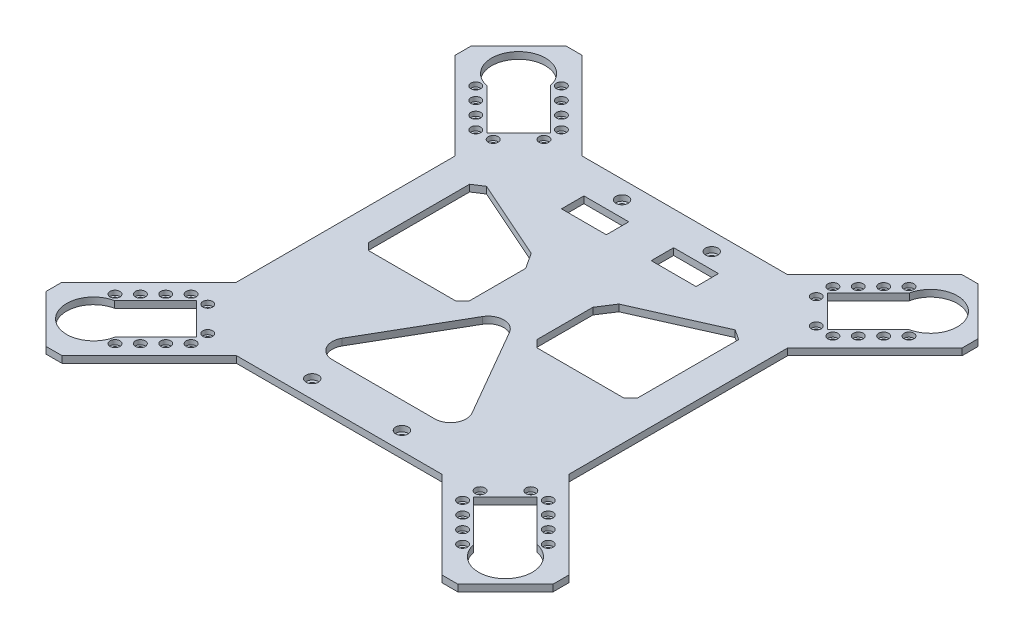
SolidWorks part; units mm, degrees
material "Thornel Mat VMA"
ref_plane "Front Plane" through (0, 0, 0) normal (0, 0, 1) x (1, 0, 0)
ref_plane "Top Plane" through (0, 0, 0) normal (0, 1, 0) x (1, 0, 0)
ref_plane "Right Plane" through (0, 0, 0) normal (1, 0, 0) x (0, 0, -1)
sketch "Sketch1" plane through (0, 0, 0) normal (0, 1, 0) x (1, 0, 0)
  line L0 (-60, 100) -> (-122.1499, 162.1499) construction
  line L1 (-74.1421, -30) -> (-74.1421, -85.8579)
  line L2 (74.1421, -30) -> (74.1421, -85.8579)
  line L5 (-60, 100) -> (60, -100) construction
  line L6 (-60, -100) -> (60, 100) construction
  line L11 (-45.8579, 114.1421) -> (-84.7487, 153.033)
  line L13 (-74.1421, 85.8579) -> (-113.033, 124.7487)
  line L14 (-91.8198, 153.033) -> (-113.033, 131.8198)
  line L15 (-84.7487, 153.033) -> (-91.8198, 153.033)
  line L16 (-113.033, 124.7487) -> (-113.033, 131.8198)
  line L17 (0, 118.7449) -> (0, 114.1421) construction
  line L18 (113.033, 124.7487) -> (113.033, 131.8198)
  line L19 (91.8198, 153.033) -> (113.033, 131.8198)
  line L20 (84.7487, 153.033) -> (91.8198, 153.033)
  line L21 (74.1421, 85.8579) -> (113.033, 124.7487)
  line L24 (45.8579, 114.1421) -> (84.7487, 153.033)
  line L25 (-95.3553, 0) -> (90.6066, 0) construction
  line L26 (-113.033, -124.7487) -> (-113.033, -131.8198)
  line L27 (-91.8198, -153.033) -> (-113.033, -131.8198)
  line L28 (-84.7487, -153.033) -> (-91.8198, -153.033)
  line L29 (-45.8579, -114.1421) -> (-84.7487, -153.033)
  line L30 (-74.1421, -85.8579) -> (-113.033, -124.7487)
  line L35 (74.1421, -85.8579) -> (113.033, -124.7487)
  line L36 (113.033, -124.7487) -> (113.033, -131.8198)
  line L37 (91.8198, -153.033) -> (113.033, -131.8198)
  line L38 (84.7487, -153.033) -> (91.8198, -153.033)
  line L39 (45.8579, -114.1421) -> (84.7487, -153.033)
  line L40 (45.8579, 114.1421) -> (-45.8579, 114.1421)
  line L41 (-45.8579, -114.1421) -> (45.8579, -114.1421)
  line L42 (74.1421, 85.8579) -> (74.1421, 30)
  line L43 (-74.1421, 85.8579) -> (-74.1421, 30)
  line L44 (74.1421, 30) -> (90.6066, 20)
  line L46 (90.6066, -20) -> (74.1421, -30)
  line L47 (90.6066, 20) -> (145.6066, 20)
  line L48 (150.6066, 15) -> (150.6066, -15)
  line L49 (145.6066, -20) -> (90.6066, -20)
  line L50 (145.6066, 20) -> (150.6066, 15)
  line L51 (150.6066, -15) -> (145.6066, -20)
  line L52 (-150.6066, -15) -> (-145.6066, -20)
  line L53 (-150.6066, 15) -> (-150.6066, -15)
  line L54 (-145.6066, 20) -> (-150.6066, 15)
  line L55 (-145.6066, -20) -> (-90.6066, -20)
  line L56 (-90.6066, 20) -> (-145.6066, 20)
  line L58 (-90.6066, -20) -> (-74.1421, -30)
  line L59 (-74.1421, 30) -> (-90.6066, 20)
  line L60 (0, 100) -> (0, -122.5689) construction
  point P0 (0, 0)
  point P12 (-88.2843, 156.5685)
  point P14 (-116.5685, 128.2843)
  point P42 (150.6066, 20)
  point P46 (150.6066, -20)
  dimension "D1" = 200
  dimension "D2" = 120
  dimension "D3" = 20
  dimension "D4" = 60
  dimension "D5" = 20
  dimension "D6" = 60
  dimension "D7" = 30
  dimension "D8" = 30
  dimension "D9" = 40
  dimension "D10" = 20
  dimension "D13" = 30
  dimension "D14" = 60
  dimension "D15" = 15
extrude "Boss-Extrude1" add sketch "Sketch1" along normal blind 3
sketch "Sketch2" plane through (0, 3, 0) normal (0, 1, 0) x (1, 0, 0)
  line L0 (150.6066, -15) -> (150.6066, 15) construction
  line L1 (103.1066, 10) -> (128.9734, 10)
  line L2 (103.1066, 10) -> (103.1066, -10)
  line L3 (103.1066, -10) -> (128.9734, -10)
  line L4 (0, 114.1421) -> (0, -114.1421) construction
  line L5 (145.6066, 20) -> (90.6066, 20) construction
  line L6 (45.8579, 114.1421) -> (-45.8579, 114.1421) construction
  line L7 (-45.8579, -114.1421) -> (45.8579, -114.1421) construction
  line L8 (-103.1066, -10) -> (-128.9734, -10)
  line L9 (-103.1066, 10) -> (-103.1066, -10)
  line L10 (-103.1066, 10) -> (-128.9734, 10)
  arc A0 (128.9734, -10) -> (128.9734, 10) centre (135.6066, 0) ccw
  arc A1 (-128.9734, -10) -> (-128.9734, 10) centre (-135.6066, 0) cw
  dimension "D1" = 24
  dimension "D2" = 15
  dimension "D3" = 20
  dimension "D4" = 10
  dimension "D5" = 32.5
  dimension "D6" = 20
extrude "Cut-Extrude1" cut sketch "Sketch2" against normal blind 10
sketch "Sketch4" plane through (0, 3, 0) normal (0, 1, 0) x (1, 0, 0)
  line L0 (-102.4264, 142.4264) -> (-100.3051, 140.3051) construction
  line L1 (-91.8198, 153.033) -> (-113.033, 131.8198) construction
  line L2 (-75.9099, 101.7678) -> (-61.7678, 115.9099)
  line L3 (-61.7678, 115.9099) -> (-80.0583, 134.2005)
  line L4 (0, 114.1421) -> (0, -114.1421) construction
  line L5 (-94.2005, 120.0583) -> (-75.9099, 101.7678)
  line L6 (-68.8388, 108.8388) -> (-51.636, 91.636) construction
  line L7 (45.8579, 114.1421) -> (-45.8579, 114.1421) construction
  line L8 (-45.8579, -114.1421) -> (45.8579, -114.1421) construction
  line L9 (68.8388, 108.8388) -> (51.636, 91.636) construction
  line L10 (102.4264, 142.4264) -> (100.3051, 140.3051) construction
  line L11 (94.2005, 120.0583) -> (75.9099, 101.7678)
  line L12 (61.7678, 115.9099) -> (80.0583, 134.2005)
  line L13 (75.9099, 101.7678) -> (61.7678, 115.9099)
  line L14 (-103.1066, 0) -> (103.1066, 0) construction
  line L15 (-103.1066, -10) -> (-103.1066, 10) construction
  line L16 (103.1066, 10) -> (103.1066, -10) construction
  line L17 (102.4264, -142.4264) -> (100.3051, -140.3051) construction
  line L18 (68.8388, -108.8388) -> (51.636, -91.636) construction
  line L19 (-68.8388, -108.8388) -> (-51.636, -91.636) construction
  line L20 (-102.4264, -142.4264) -> (-100.3051, -140.3051) construction
  line L21 (75.9099, -101.7678) -> (61.7678, -115.9099)
  line L22 (61.7678, -115.9099) -> (80.0583, -134.2005)
  line L23 (94.2005, -120.0583) -> (75.9099, -101.7678)
  line L24 (-94.2005, -120.0583) -> (-75.9099, -101.7678)
  line L25 (-61.7678, -115.9099) -> (-80.0583, -134.2005)
  line L26 (-75.9099, -101.7678) -> (-61.7678, -115.9099)
  arc A0 (-80.0583, 134.2005) -> (-94.2005, 120.0583) centre (-91.8198, 131.8198) ccw
  arc A1 (80.0583, 134.2005) -> (94.2005, 120.0583) centre (91.8198, 131.8198) cw
  arc A2 (80.0583, -134.2005) -> (94.2005, -120.0583) centre (91.8198, -131.8198) ccw
  arc A3 (-80.0583, -134.2005) -> (-94.2005, -120.0583) centre (-91.8198, -131.8198) cw
  dimension "D1" = 24
  dimension "D2" = 15
  dimension "D3" = 32.5
  dimension "D4" = 20
  dimension "D5" = 10
extrude "Cut-Extrude2" cut sketch "Sketch4" against normal blind 10
hole_wizard "CBORE for M2 SHCS1" positions "Sketch7" profile "Sketch6" counterbore size "M2" standard "Ansi Metric" end condition through all
sketch "Sketch7" plane through (0, 3, 0) normal (0, 1, 0) x (-1, 0, 0)
  line L0 (-128.9734, -10) -> (-103.1066, -10) construction
  line L1 (-103.1066, -10) -> (-103.1066, 10) construction
  line L2 (-103.1066, 10) -> (-128.9734, 10) construction
  line L3 (-80.0583, -134.2005) -> (-61.7678, -115.9099) construction
  line L4 (-61.7678, -115.9099) -> (-75.9099, -101.7678) construction
  line L5 (-75.9099, -101.7678) -> (-94.2005, -120.0583) construction
  point P0 (-104.8566, -13.5)
  point P1 (-112.8566, -13.5)
  point P3 (-120.8566, -13.5)
  point P5 (-128.8566, -13.5)
  point P7 (-60.5303, -119.6222)
  point P9 (-66.1872, -125.2791)
  point P11 (-71.844, -130.9359)
  point P13 (-77.5009, -136.5928)
  point P15 (-79.6222, -100.5303)
  point P17 (-85.2791, -106.1872)
  point P19 (-90.9359, -111.844)
  point P21 (-96.5928, -117.5009)
  point P31 (-104.8566, 13.5)
  point P33 (-112.8566, 13.5)
  point P35 (-120.8566, 13.5)
  point P37 (-128.8566, 13.5)
  point P59 (-60.7071, -112.0208)
  point P61 (-72.0208, -100.7071)
  point P63 (-99.6066, -8)
  point P65 (-99.6066, 8)
  dimension "D1" = 3.5
  dimension "D2" = 8
  dimension "D3" = 8
  dimension "D4" = 8
  dimension "D5" = 3.5
  dimension "D6" = 1.75
  dimension "D7" = 8
  dimension "D8" = 8
  dimension "D9" = 8
  dimension "D10" = 1.75
  dimension "D11" = 3.5
  dimension "D12" = 8
  dimension "D13" = 8
  dimension "D14" = 8
  dimension "D15" = 3.5
  dimension "D16" = 3.5
  dimension "D17" = 3.5
  dimension "D18" = 3.5
  dimension "D19" = 1.75
  dimension "D20" = 8
  dimension "D21" = 8
  dimension "D22" = 8
  dimension "D23" = 3.5
  dimension "D24" = 3.5
  dimension "D25" = 3.5
  dimension "D26" = 3.5
  dimension "D27" = 1.75
  dimension "D28" = 3.5
  dimension "D29" = 3.5
  dimension "D30" = 2
  dimension "D31" = 2
  dimension "D32" = 3.5
  dimension "D33" = 3.5
  dimension "D34" = 2
  dimension "D35" = 2
sketch "Sketch6" plane through (104.8566, 3, -13.5) normal (1, 0, 0) x (0, 0, 1)
  line L0 (0, 0) -> (0, 3)
  line L1 (0, 3) -> (1.2, 3)
  line L3 (1.2, 3) -> (1.2, 2)
  line L4 (1.2, 2) -> (2.2, 2)
  line L5 (2.2, 2) -> (2.2, 0)
  line L7 (2.2, 0) -> (0, 0)
  line L11 (0, -6.35) -> (0, 107.95) construction
  dimension "Thru Hole Dia." = 2.4
  dimension "Thru Hole Depth" = 3
  dimension "C'Bore Dia." = 4.4
  dimension "C'Bore Depth" = 2
mirror "Mirror1" about plane through (0, 0, 0) normal (1, 0, 0) of "CBORE for M2 SHCS1"
mirror "Mirror2" about plane through (0, 0, 0) normal (0, 0, 1) of "Mirror1", "CBORE for M2 SHCS1"
sketch "Sketch8" plane through (0, 3, 0) normal (0, 1, 0) x (1, 0, 0)
  line L0 (-45.8579, -114.1421) -> (45.8579, -114.1421) construction
  line L1 (30, -99.1421) -> (10, -99.1421)
  line L2 (30, -99.1421) -> (30, -89.1421)
  line L3 (30, -89.1421) -> (10, -89.1421)
  line L4 (10, -99.1421) -> (10, -89.1421)
  line L5 (-10, -99.1421) -> (-30, -99.1421)
  line L6 (-10, -99.1421) -> (-10, -89.1421)
  line L7 (-10, -89.1421) -> (-30, -89.1421)
  line L8 (-30, -99.1421) -> (-30, -89.1421)
  line L9 (-45.8579, -114.1421) -> (45.8579, -114.1421) construction
  line L10 (-20, -28.1625) -> (-55, -28.1625)
  line L11 (30, -20) -> (-30, -20)
  line L12 (30, -20) -> (30, -10)
  line L13 (30, -10) -> (-30, -10)
  line L14 (-30, -20) -> (-30, -10)
  line L15 (-60, -33.1625) -> (-60, -78.1625)
  line L16 (-55.4309, -81.1318) -> (-19.5691, -65.1932)
  line L17 (-15, -58.1625) -> (-15, -33.1625)
  line L18 (-60, -78.1625) -> (-55.4309, -81.1318)
  line L19 (-19.5691, -65.1932) -> (-15, -58.1625)
  line L20 (-15, -33.1625) -> (-20, -28.1625)
  line L21 (-55, -28.1625) -> (-60, -33.1625)
  line L22 (55, -28.1625) -> (20, -28.1625)
  line L23 (15, -33.1625) -> (15, -58.1625)
  line L24 (19.5691, -65.1932) -> (55.4309, -81.1318)
  line L25 (60, -78.1625) -> (60, -33.1625)
  line L26 (55.4309, -81.1318) -> (60, -78.1625)
  line L27 (15, -58.1625) -> (19.5691, -65.1932)
  line L28 (20, -28.1625) -> (15, -33.1625)
  line L29 (60, -33.1625) -> (55, -28.1625)
  line L30 (84.5185, 0) -> (-74.8348, 0) construction
  line L31 (-20, 28.1625) -> (-55, 28.1625)
  line L32 (-55, 28.1625) -> (-60, 33.1625)
  line L33 (-60, 33.1625) -> (-60, 78.1625)
  line L34 (-60, 78.1625) -> (-55.4309, 81.1318)
  line L35 (-55.4309, 81.1318) -> (-19.5691, 65.1932)
  line L36 (-19.5691, 65.1932) -> (-15, 58.1625)
  line L37 (-15, 58.1625) -> (-15, 33.1625)
  line L38 (-15, 33.1625) -> (-20, 28.1625)
  line L39 (20, 28.1625) -> (15, 33.1625)
  line L40 (15, 33.1625) -> (15, 58.1625)
  line L41 (15, 58.1625) -> (19.5691, 65.1932)
  line L42 (19.5691, 65.1932) -> (55.4309, 81.1318)
  line L43 (55.4309, 81.1318) -> (60, 78.1625)
  line L44 (60, 78.1625) -> (60, 33.1625)
  line L45 (60, 33.1625) -> (55, 28.1625)
  line L46 (55, 28.1625) -> (20, 28.1625)
  line L47 (30, 99.1421) -> (10, 99.1421)
  line L48 (30, 99.1421) -> (30, 89.1421)
  line L49 (30, 89.1421) -> (10, 89.1421)
  line L50 (10, 99.1421) -> (10, 89.1421)
  line L51 (-10, 99.1421) -> (-10, 89.1421)
  line L52 (-10, 99.1421) -> (-30, 99.1421)
  line L53 (-30, 99.1421) -> (-30, 89.1421)
  line L54 (-10, 89.1421) -> (-30, 89.1421)
  point P10 (0, -114.1421)
  point P13 (0, -114.1421)
  point P18 (-15, -28.1625)
  point P20 (-60, -28.1625)
  point P22 (-60, -83.1625)
  point P23 (-15, -63.1625)
  point P31 (60, -28.1625)
  point P32 (15, -28.1625)
  point P34 (15, -63.1625)
  point P35 (60, -83.1625)
  dimension "D1" = 20
  dimension "D2" = 20
  dimension "D3" = 15
  dimension "D4" = 15
  dimension "D5" = 10
  dimension "D6" = 10
  dimension "D7" = 10
  dimension "D8" = 10
  dimension "D9" = 10
  dimension "D10" = 60
  dimension "D11" = 10
  dimension "D12" = 45
  dimension "D13" = 55
  dimension "D14" = 35
  dimension "D15" = 55
  dimension "D16" = 35
  dimension "D17" = 45
  dimension "D18" = 15
  dimension "D23" = 15
extrude "Cut-Extrude3" cut sketch "Sketch8" against normal blind 10
hole_wizard "CBORE for M2.5 SHCS1" positions "Sketch11" profile "Sketch10" counterbore size "M2.5" standard "Ansi Metric" end condition through all
sketch "Sketch11" plane through (0, 3, 0) normal (0, 1, 0) x (-1, 0, 0)
  line L0 (30, 99.1421) -> (10, 99.1421) construction
  line L1 (-10, 99.1421) -> (-30, 99.1421) construction
  line L2 (10, -99.1421) -> (30, -99.1421) construction
  line L3 (-30, -99.1421) -> (-10, -99.1421) construction
  point P0 (20, -106.1421)
  point P1 (-20, -106.1421)
  point P3 (20, 106.1421)
  point P5 (-20, 106.1421)
  dimension "D1" = 7
  dimension "D2" = 7
  dimension "D3" = 10
  dimension "D4" = 10
  dimension "D5" = 7
  dimension "D6" = 7
  dimension "D7" = 10
  dimension "D8" = 10
sketch "Sketch10" plane through (-20, 3, -106.1421) normal (1, 0, 0) x (0, 0, 1)
  line L0 (0, 0) -> (0, 3)
  line L1 (0, 3) -> (1.45, 3)
  line L3 (1.45, 3) -> (1.45, 2.5)
  line L4 (1.45, 2.5) -> (2.75, 2.5)
  line L5 (2.75, 2.5) -> (2.75, 0)
  line L7 (2.75, 0) -> (0, 0)
  line L11 (0, -6.35) -> (0, 107.95) construction
  dimension "Thru Hole Dia." = 2.9
  dimension "Thru Hole Depth" = 3
  dimension "C'Bore Dia." = 5.5
  dimension "C'Bore Depth" = 2.5
sketch "Croquis1" plane through (0, 3, 0) normal (0, 1, 0) x (-1, 0, 0)
  line L0 (186.8809, -30) -> (-169.671, -30)
  line L2 (-169.671, -30) -> (-169.671, 164.8)
  line L3 (-169.671, 164.8) -> (186.8809, 164.8)
  line L4 (186.8809, 164.8) -> (186.8809, -30)
extrude "Cortar-Extruir1" cut sketch "Croquis1" along normal blind 848 and the other way blind 962
sketch "Croquis3" plane through (0, 3, 0) normal (0, 1, 0) x (1, 0, 0)
  line L0 (-74.1421, -40) -> (-74.1421, 30)
  line L2 (-74.1421, 30) -> (74.1421, 30)
  line L3 (74.1421, 30) -> (74.1421, -40)
  line L4 (-74.1421, -40) -> (74.1421, -40)
  line L6 (-74.1421, -40) -> (74.1421, -40)
  line L7 (-74.1421, -40) -> (-74.1421, 30)
  line L8 (-74.1421, 30) -> (74.1421, 30)
  line L9 (74.1421, -40) -> (74.1421, 30)
extrude "Saliente-Extruir3" add sketch "Croquis3" against normal blind 3 contours L0 L4 L3 L2 region at (0, 3, 5)
sketch "Croquis5" plane through (0, 3, 0) normal (0, 1, 0) x (-1, 0, 0)
  line L0 (45.8579, -114.1421) -> (45.8579, 40) construction
  line L1 (74.1421, 40) -> (-74.1421, 40) construction
  line L2 (-45.8579, -114.1421) -> (-45.8579, 40) construction
sketch "Croquis7" plane through (0, 3, 0) normal (0, 1, 0) x (-1, 0, 0)
  line L0 (-74.1421, -85.8579) -> (-45.8579, -85.8579) construction
  line L1 (-45.8579, -114.1421) -> (-45.8579, 40) construction
  line L2 (-45.8579, 40) -> (-45.8579, 11.7157) construction
  line L3 (-45.8579, 11.7157) -> (-74.1421, 11.7157) construction
  line L4 (-74.1421, 40) -> (-74.1421, -85.8579) construction
  line L5 (-74.1421, 11.7157) -> (-45.8579, 11.7157) construction
  line L6 (-45.8579, 11.7157) -> (74.1421, 11.7157) construction
  line L7 (74.1421, -85.8579) -> (74.1421, 40) construction
  line L8 (74.1421, 11.7157) -> (45.8579, 40) construction
  line L9 (-74.1421, 11.7157) -> (-45.8579, 40) construction
  line L10 (-45.8579, 11.7157) -> (-102.4264, 68.2843) construction
  line L11 (-45.8579, -85.8579) -> (-102.4264, -142.4264) construction
  line L12 (-113.033, -131.8198) -> (-91.8198, -153.033) construction
  line L13 (-102.4264, 68.2843) -> (-91.8198, 78.8909)
  line L14 (-45.8579, 40) -> (-84.7487, 78.8909)
  line L15 (-113.033, 50.6066) -> (-74.1421, 11.7157)
  line L16 (-84.7487, 78.8909) -> (-84.4653, 78.9354)
  line L17 (-113.033, -131.8198) -> (-132.5778, -112.275) construction
  line L18 (-74.1421, -85.8579) -> (-138.5229, -150.2386) construction
  line L19 (-45.8579, 40) -> (-74.1421, 11.7157)
  line L20 (-91.8198, 78.8909) -> (-84.7487, 78.8909)
  line L21 (-74.1421, 11.7157) -> (-113.033, 50.6066)
  line L22 (-113.033, 57.6777) -> (-102.4264, 68.2843)
  line L23 (-113.033, 57.6777) -> (-113.033, 50.6066)
  dimension "D1" = 28.2843
  dimension "D2" = 28.2843
extrude "Saliente-Extruir4" add sketch "Croquis7" against normal blind 3 contours L22 L23 L15 L19 L14 L20 L13 region at (81.0023, 3, 46.8602)
sketch "Croquis9" plane through (0, 3, 0) normal (0, 1, 0) x (-1, 0, 0)
  line L0 (-102.4264, 68.2843) -> (-38.465, 4.3229) construction
  line L1 (-113.033, 57.6777) -> (-91.8198, 78.8909) construction
  line L2 (-74.1421, 11.7157) -> (-45.8579, 40) construction
  line L3 (-45.8579, -114.1421) -> (-74.1421, -85.8579) construction
  line L4 (-60, 25.8579) -> (-68.8388, 34.6967) construction
  line L5 (-60, 25.8579) -> (-91.8198, 57.6777) construction
  line L6 (-60, -100) -> (-68.8388, -108.8388) construction
  line L7 (-61.7678, -115.9099) -> (-75.9099, -101.7678) construction
  line L8 (-68.8388, 34.6967) -> (-75.9099, 27.6256) construction
  line L9 (-68.8388, 34.6967) -> (-61.7678, 41.7678) construction
  line L10 (-61.7678, 41.7678) -> (-75.9099, 27.6256)
  line L11 (-61.7678, 41.7678) -> (-86.1616, 66.1616) construction
  line L12 (-75.9099, 27.6256) -> (-95.9758, 47.6915) construction
  line L13 (-61.7678, 41.7678) -> (-80.0583, 60.0583)
  line L14 (-75.9099, 27.6256) -> (-94.2005, 45.9162)
  line L15 (-68.8388, -108.8388) -> (-91.8198, -131.8198) construction
  arc A0 (-94.2005, 45.9162) -> (-80.0583, 60.0583) centre (-91.8198, 57.6777) cw
  dimension "D1" = 12
  dimension "D2" = 10
  dimension "D3" = 10
extrude "Cortar-Extruir3" cut sketch "Croquis9" against normal blind 3
sketch "Croquis10" plane through (0, 3, 0) normal (0, 1, 0) x (-1, 0, 0)
  line L0 (-105.6578, 43.2313) -> (-101.0616, 47.8275) construction
  line L1 (-60.5303, -119.6222) -> (-50.4541, -109.5459) construction
  line L2 (-59.0233, -127.3076) -> (-63.7541, -122.846) construction
  line L3 (-84.7487, -153.033) -> (-45.8579, -114.1421) construction
  line L4 (-45.8579, -114.1421) -> (-74.1421, -85.8579) construction
  line L5 (-66.1872, -125.2791) -> (-14.5561, -155.2155) construction
  line L6 (-113.033, 50.6066) -> (-74.1421, 11.7157) construction
  line L7 (-101.0616, 47.8275) -> (-69.5459, 16.3119) construction
  line L8 (-69.5459, 16.3119) -> (-79.6222, 26.3882) construction
  line L9 (-79.6222, 26.3882) -> (-85.2791, 32.045) construction
  line L10 (-74.1421, 11.7157) -> (-69.5459, 16.3119) construction
  line L11 (-69.5459, 16.3119) -> (-45.8579, 40) construction
  line L12 (-85.2791, 32.045) -> (-90.9359, 37.7019) construction
  line L13 (-90.9359, 37.7019) -> (-96.5928, 43.3588) construction
  circle A0 centre (-79.6222, 26.3882) radius 1.2
  circle A1 centre (-85.2791, 32.045) radius 1.2
  circle A2 centre (-90.9359, 37.7019) radius 1.2
  circle A3 centre (-96.5928, 43.3588) radius 1.2
  dimension "D3" = 14.25
  dimension "D5" = 8
  dimension "D7" = 2.4
  dimension "D9" = 2.4
  dimension "D10" = 2.4
  dimension "D8" = 2.4
  dimension "D1" = 6.5
  dimension "D2" = 6.5
  dimension "D4" = 8
  dimension "D6" = 8
extrude "Cortar-Extruir13" cut sketch "Croquis10" against normal blind 3
sketch "Croquis22" plane through (0, 3, 0) normal (0, 1, 0) x (-1, 0, 0)
  circle A0 centre (-79.6222, 26.3882) radius 2.2
  circle A1 centre (-85.2791, 32.045) radius 2.2
  circle A2 centre (-90.9359, 37.7019) radius 2.2
  circle A3 centre (-96.5928, 43.3588) radius 2.2
  dimension "D1" = 4.4
  dimension "D2" = 4.4
  dimension "D3" = 4.4
  dimension "D4" = 4.4
extrude "Cortar-Extruir14" cut sketch "Croquis22" against normal blind 2
sketch "Croquis23" plane through (0, 3, 0) normal (0, 1, 0) x (-1, 0, 0)
  line L1 (6.0622, -29.9145) -> (28.9378, 9.7073)
  line L2 (22.8756, 20.2073) -> (-22.8756, 20.2073)
  line L3 (-28.9378, 9.7073) -> (-6.0622, -29.9145)
  circle A0 centre (0, 0) radius 20.2073 construction
  arc A1 (-6.0622, -29.9145) -> (6.0622, -29.9145) centre (0, -26.4145) ccw
  arc A2 (22.8756, 20.2073) -> (28.9378, 9.7073) centre (22.8756, 13.2073) cw
  arc A3 (-22.8756, 20.2073) -> (-28.9378, 9.7073) centre (-22.8756, 13.2073) ccw
  dimension "D1" = 7
  dimension "D2" = 7
  dimension "D3" = 7
extrude "Cortar-Extruir16" cut sketch "Croquis23" along normal blind 243 and the other way blind 68
sketch "Croquis25" plane through (0, 3, 0) normal (0, 1, 0) x (-1, 0, 0)
  line L0 (-45.8579, -114.1421) -> (-74.1421, -85.8579) construction
  line L1 (-74.1421, -85.8579) -> (-113.033, -124.7487) construction
  line L2 (-50.4541, 35.4038) -> (-60.5303, 45.4801) construction
  line L3 (-78.3584, 72.5005) -> (-82.9546, 67.9043) construction
  line L4 (-45.8579, 40) -> (-84.7487, 78.8909) construction
  line L5 (-45.8579, 40) -> (-50.4541, 35.4038) construction
  line L6 (-60.5303, 45.4801) -> (-66.1872, 51.1369) construction
  line L7 (-66.1872, 51.1369) -> (-71.844, 56.7938) construction
  line L8 (-71.844, 56.7938) -> (-79.9053, 64.8551) construction
  circle A0 centre (-60.5303, 45.4801) radius 1.2
  circle A1 centre (-66.1872, 51.1369) radius 1.2
  circle A2 centre (-71.844, 56.7938) radius 1.2
  dimension "D4" = 2.4
  dimension "D6" = 2.4
  dimension "D7" = 2.4
  dimension "D1" = 6.5
  dimension "D2" = 6.5
  dimension "D3" = 14.25
  dimension "D5" = 8
  dimension "D8" = 8
  dimension "D11" = 11.4004
extrude "Cortar-Extruir17" cut sketch "Croquis25" against normal blind 3
sketch "Croquis26" plane through (0, 3, 0) normal (0, 1, 0) x (-1, 0, 0)
  line L0 (-71.844, 56.7938) -> (-77.5009, 62.4506) construction
  circle A0 centre (-77.5009, 62.4506) radius 1.2
  dimension "D2" = 2.4
  dimension "D1" = 8
extrude "Cortar-Extruir18" cut sketch "Croquis26" against normal blind 3
sketch "Croquis27" plane through (0, 3, 0) normal (0, 1, 0) x (-1, 0, 0)
  circle A0 centre (-60.5303, 45.4801) radius 2.2
  circle A1 centre (-66.1872, 51.1369) radius 2.2
  circle A2 centre (-71.844, 56.7938) radius 2.2
  circle A3 centre (-77.5009, 62.4506) radius 2.2
  dimension "D1" = 4.4
  dimension "D2" = 4.4
  dimension "D3" = 4.4
  dimension "D4" = 4.4
extrude "Cortar-Extruir19" cut sketch "Croquis27" against normal blind 2
sketch "Croquis29" plane through (0, 3, 0) normal (0, 1, 0) x (-1, 0, 0)
  line L0 (-54.3431, 31.5147) -> (-60.7071, 37.8787) construction
  line L1 (-45.8579, 40) -> (-54.3431, 31.5147) construction
  line L2 (-74.1421, 11.7157) -> (-65.6569, 20.201) construction
  line L3 (-65.6569, 20.201) -> (-72.0208, 26.565) construction
  circle A0 centre (-60.7071, 37.8787) radius 1.2
  circle A1 centre (-72.0208, 26.565) radius 1.2
  dimension "D5" = 2.4
  dimension "D6" = 2.4
  dimension "D1" = 12
  dimension "D2" = 12
  dimension "D3" = 9
  dimension "D4" = 9
extrude "Cortar-Extruir20" cut sketch "Croquis29" against normal blind 3
sketch "Croquis30" plane through (0, 3, 0) normal (0, 1, 0) x (-1, 0, 0)
  circle A0 centre (-60.7071, 37.8787) radius 2.2
  circle A1 centre (-72.0208, 26.565) radius 2.2
  dimension "D1" = 4.4
  dimension "D2" = 4.4
extrude "Cortar-Extruir21" cut sketch "Croquis30" against normal blind 2
sketch "Croquis31" plane through (0, 3, 0) normal (0, 1, 0) x (-1, 0, 0)
  line L0 (45.8579, 40) -> (74.1421, 11.7157) construction
  line L1 (74.1421, -85.8579) -> (74.1421, 40) construction
  line L2 (113.033, 50.6066) -> (74.1421, 11.7157)
  line L3 (113.033, 50.6066) -> (113.033, 57.6777)
  line L4 (84.7487, 78.8909) -> (45.8579, 40)
  line L5 (113.033, 57.6777) -> (91.8198, 78.8909)
  line L6 (-45.8579, 40) -> (-74.1421, 11.7157) construction
  line L7 (-74.1421, 11.7157) -> (-60, 25.8579) construction
  line L8 (84.7487, 78.8909) -> (91.8198, 78.8909)
  line L9 (45.8579, 40) -> (74.1421, 11.7157)
  line L10 (116.5685, 54.1421) -> (113.033, 50.6066) construction
  line L11 (91.8198, 78.8909) -> (90.5208, 79.2734)
  line L12 (88.2843, 82.4264) -> (84.7487, 78.8909) construction
  dimension "D1" = 60
  dimension "D2" = 5
  dimension "D3" = 5
extrude "Saliente-Extruir5" add sketch "Croquis31" against normal blind 3 contours L4 L9 L2 L3 L5 L8 region at (-81.0023, 3, 46.8602)
sketch "Croquis33" plane through (0, 3, 0) normal (0, 1, 0) x (-1, 0, 0)
  line L0 (74.1421, 11.7157) -> (45.8579, 40) construction
  line L1 (45.8579, 40) -> (60, 25.8579) construction
  line L2 (60, 25.8579) -> (68.8388, 34.6967) construction
  line L4 (-45.8579, 40) -> (-74.1421, 11.7157) construction
  line L5 (-68.8388, 34.6967) -> (-60, 25.8579) construction
  line L6 (-75.9099, 27.6256) -> (-61.7678, 41.7678) construction
  line L7 (74.1421, -85.8579) -> (45.8579, -114.1421) construction
  line L8 (68.8388, 34.6967) -> (61.7678, 41.7678) construction
  line L9 (68.8388, 34.6967) -> (75.9099, 27.6256) construction
  line L10 (102.4264, 68.2843) -> (91.8198, 57.6777) construction
  line L11 (113.033, 57.6777) -> (91.8198, 78.8909) construction
  line L12 (75.9099, 27.6256) -> (94.2005, 45.9162)
  line L13 (61.7678, 41.7678) -> (80.0583, 60.0583)
  line L14 (75.9099, 27.6256) -> (61.7678, 41.7678)
  arc A0 (80.0583, 60.0583) -> (93.8886, 45.8573) centre (91.8198, 57.6777) cw
  dimension "D5" = 12
  dimension "D1" = 12.5
  dimension "D2" = 10
  dimension "D3" = 10
  dimension "D4" = 15
extrude "Cortar-Extruir22" cut sketch "Croquis33" against normal blind 3 contours A0 L13 L14 L12 region at (-84.3424, 3, 50.2003)
sketch "Croquis34" plane through (0, 3, 0) normal (0, 1, 0) x (-1, 0, 0)
  line L0 (50.4541, 35.4038) -> (60.5303, 45.4801) construction
  line L1 (45.8579, 40) -> (50.4541, 35.4038) construction
  line L2 (60.5303, 45.4801) -> (66.1872, 51.1369) construction
  line L3 (66.1872, 51.1369) -> (71.844, 56.7938) construction
  line L4 (71.844, 56.7938) -> (77.5009, 62.4506) construction
  circle A0 centre (60.5303, 45.4801) radius 1.2
  circle A1 centre (66.1872, 51.1369) radius 1.2
  circle A2 centre (71.844, 56.7938) radius 1.2
  circle A3 centre (77.5009, 62.4506) radius 1.2
  dimension "D4" = 2.4
  dimension "D7" = 2.4
  dimension "D8" = 2.4
  dimension "D9" = 2.4
  dimension "D1" = 6.5
  dimension "D2" = 14.25
  dimension "D3" = 8
  dimension "D5" = 8
  dimension "D6" = 8
extrude "Cortar-Extruir24" cut sketch "Croquis34" against normal blind 3
sketch "Croquis35" plane through (0, 3, 0) normal (0, 1, 0) x (-1, 0, 0)
  circle A0 centre (60.5303, 45.4801) radius 2.2
  circle A1 centre (66.1872, 51.1369) radius 2.2
  circle A2 centre (71.844, 56.7938) radius 2.2
  circle A3 centre (77.5009, 62.4506) radius 2.2
  dimension "D1" = 4.4
  dimension "D2" = 4.4
  dimension "D3" = 4.4
  dimension "D4" = 4.4
extrude "Cortar-Extruir25" cut sketch "Croquis35" against normal blind 2
sketch "Croquis37" plane through (0, 3, 0) normal (0, 1, 0) x (-1, 0, 0)
  line L0 (69.5459, 16.3119) -> (79.6222, 26.3882) construction
  line L1 (74.1421, 11.7157) -> (69.5459, 16.3119) construction
  line L2 (79.6222, 26.3882) -> (85.2791, 32.045) construction
  line L3 (85.2791, 32.045) -> (90.9359, 37.7019) construction
  line L4 (90.9359, 37.7019) -> (96.5928, 43.3588) construction
  line L5 (96.5928, 43.3588) -> (-96.5928, 43.3588) construction
  line L6 (-96.5928, 43.3588) -> (-96.5928, -117.5009) construction
  line L7 (-96.5928, -117.5009) -> (96.5928, -117.5009) construction
  circle A0 centre (79.6222, 26.3882) radius 1.2
  circle A1 centre (85.2791, 32.045) radius 1.2
  circle A2 centre (90.9359, 37.7019) radius 1.2
  circle A3 centre (96.5928, 43.3588) radius 1.2
  dimension "D6" = 2.4
  dimension "D7" = 2.4
  dimension "D8" = 2.4
  dimension "D9" = 2.4
  dimension "D1" = 6.5
  dimension "D2" = 14.25
  dimension "D3" = 8
  dimension "D4" = 8
  dimension "D5" = 8
extrude "Cortar-Extruir26" cut sketch "Croquis37" against normal blind 3
sketch "Croquis38" plane through (0, 3, 0) normal (0, 1, 0) x (-1, 0, 0)
  circle A0 centre (79.6222, 26.3882) radius 2.2
  circle A1 centre (85.2791, 32.045) radius 2.2
  circle A2 centre (90.9359, 37.7019) radius 2.2
  circle A3 centre (96.5928, 43.3588) radius 2.2
  dimension "D1" = 4.4
  dimension "D2" = 4.4
  dimension "D3" = 4.4
  dimension "D4" = 4.4
extrude "Cortar-Extruir27" cut sketch "Croquis38" against normal blind 2
sketch "Croquis39" plane through (0, 3, 0) normal (0, 1, 0) x (-1, 0, 0)
  line L0 (74.1421, -85.8579) -> (45.8579, -114.1421) construction
  line L1 (65.6569, 20.201) -> (72.0208, 26.565) construction
  line L2 (74.1421, 11.7157) -> (65.6569, 20.201) construction
  line L3 (45.8579, 40) -> (54.3431, 31.5147) construction
  line L4 (54.3431, 31.5147) -> (60.7071, 37.8787) construction
  circle A0 centre (72.0208, 26.565) radius 1.2
  circle A1 centre (60.7071, 37.8787) radius 1.2
  dimension "D5" = 2.4
  dimension "D6" = 2.4
  dimension "D1" = 12
  dimension "D2" = 12
  dimension "D3" = 9
  dimension "D4" = 9
extrude "Cortar-Extruir28" cut sketch "Croquis39" against normal blind 3
sketch "Croquis40" plane through (0, 3, 0) normal (0, 1, 0) x (-1, 0, 0)
  circle A0 centre (72.0208, 26.565) radius 2.2
  circle A1 centre (60.7071, 37.8787) radius 2.2
  dimension "D1" = 4.4
  dimension "D2" = 4.4
extrude "Cortar-Extruir30" cut sketch "Croquis40" against normal blind 2
sketch "Croquis47" plane through (0, 3, 0) normal (0, 1, 0) x (-1, 0, 0)
  line L1 (45.8579, 40) -> (-45.8579, 40) construction
  line L4 (20, 40) -> (20, 32) construction
  line L5 (-20, 40) -> (-20, 32) construction
  circle A0 centre (20, 32) radius 1.45
  circle A1 centre (-20, 32) radius 1.45
  dimension "D3" = 2.9
  dimension "D4" = 2.9
  dimension "D1" = 8
  dimension "D2" = 8
extrude "Cortar-Extruir32" cut sketch "Croquis47" against normal blind 3
sketch "Croquis48" plane through (0, 3, 0) normal (0, 1, 0) x (-1, 0, 0)
  circle A0 centre (20, 32) radius 2.75
  circle A1 centre (-20, 32) radius 2.75
  dimension "D1" = 5.5
  dimension "D2" = 5.5
extrude "Cortar-Extruir33" cut sketch "Croquis48" against normal blind 2.5
